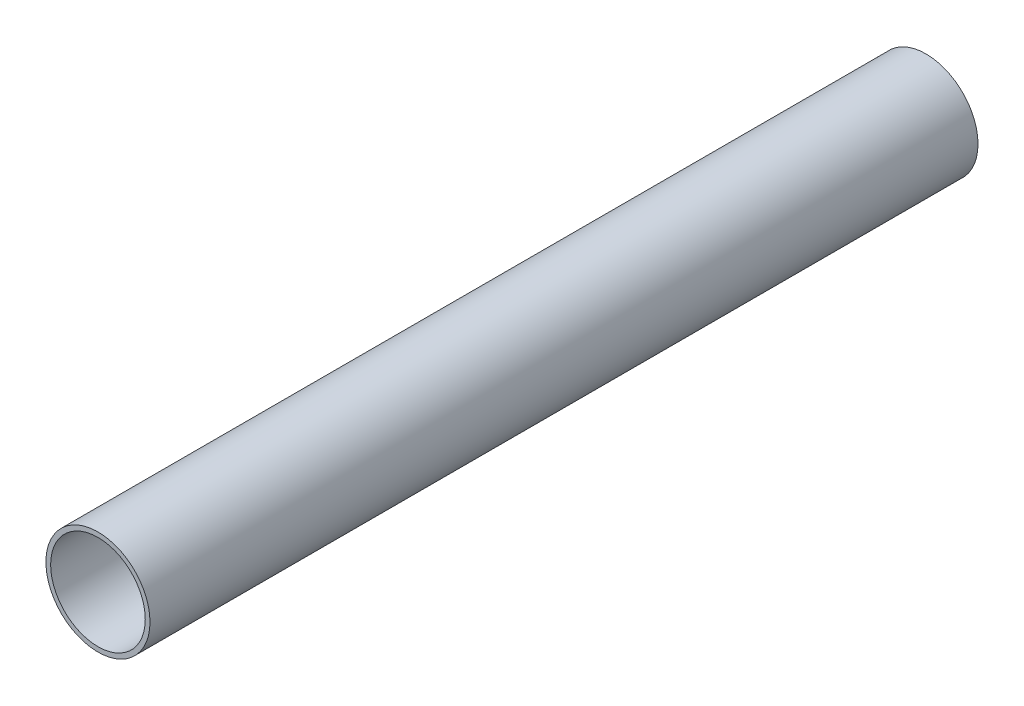
SolidWorks part; units mm, degrees
ref_plane "Front Plane" through (0, 0, 0) normal (0, 0, 1) x (1, 0, 0)
ref_plane "Top Plane" through (0, 0, 0) normal (0, 1, 0) x (1, 0, 0)
ref_plane "Right Plane" through (0, 0, 0) normal (1, 0, 0) x (0, 0, -1)
sketch "Sketch1" plane through (0, 0, 0) normal (0, 0, 1) x (1, 0, 0)
  circle A0 centre (0, 0) radius 22
  circle A1 centre (0, 0) radius 20
  dimension "D1" = 44
  dimension "D2" = 40
extrude "Boss-Extrude1" add sketch "Sketch1" along normal blind 350
fillet "Fillet1" radius 3 1 edges at (20, 0, 0)
